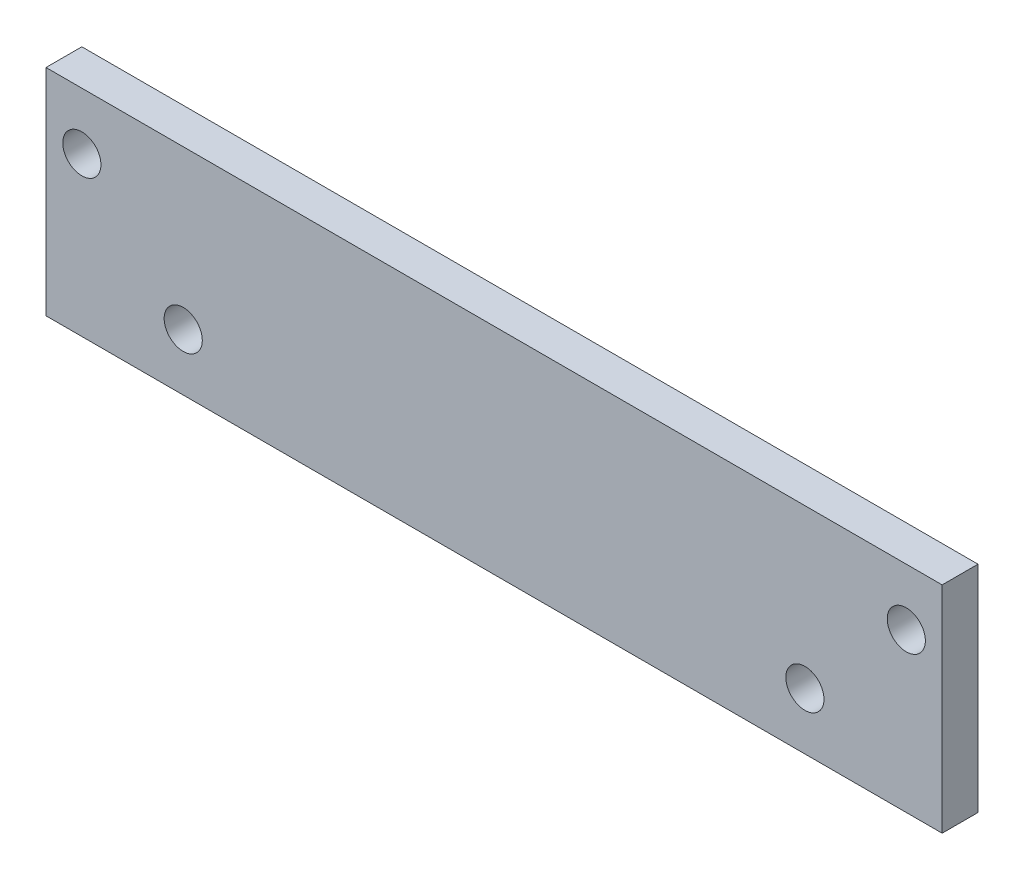
SolidWorks part; units mm, degrees
ref_plane "Front" through (0, 0, 0) normal (0, 0, 1) x (1, 0, 0)
ref_plane "Top" through (0, 0, 0) normal (0, 1, 0) x (1, 0, 0)
ref_plane "Right" through (0, 0, 0) normal (1, 0, 0) x (0, 0, -1)
sketch "Sketch1" plane through (0, 0, 0) normal (0, 0, 1) x (1, 0, 0)
  line L1 (-79.375, -19.05) -> (79.375, -19.05)
  line L2 (-79.375, -19.05) -> (-79.375, 19.05)
  line L3 (-79.375, 19.05) -> (79.375, 19.05)
  line L4 (79.375, -19.05) -> (79.375, 19.05)
  line L5 (-79.375, -19.05) -> (79.375, 19.05) construction
  line L6 (-79.375, 19.05) -> (79.375, -19.05) construction
  point P0 (0, 0)
  dimension "D1" = 158.75
  dimension "D2" = 38.1
extrude "Boss-Extrude1" add sketch "Sketch1" along normal blind 6.35
sketch "Sketch2" plane through (0, 0, 6.35) normal (0, 0, 1) x (1, 0, 0)
  line L0 (-73.025, 19.05) -> (-73.025, 8.9803) construction
  line L1 (79.375, 19.05) -> (-79.375, 19.05) construction
  line L2 (-73.025, 8.9803) -> (-55.0645, -8.9803) construction
  line L3 (-55.0645, -8.9803) -> (-55.0645, -19.05) construction
  line L4 (-79.375, -19.05) -> (79.375, -19.05) construction
  line L5 (-79.375, 19.05) -> (-79.375, -19.05) construction
  dimension "D1" = 135
  dimension "D2" = 25.4
  dimension "D3" = 6.35
hole_wizard "1/4 Clearance Hole1" positions "Sketch4" profile "Sketch3" hole size "1/4" standard "ANSI Inch" end condition through all
sketch "Sketch4" plane through (0, 0, 6.35) normal (0, 0, 1) x (1, 0, 0)
  point P0 (-73.025, 8.9803)
  point P3 (-55.0645, -8.9803)
sketch "Sketch3" plane through (-73.025, 8.9803, 6.35) normal (1, 0, 0) x (0, -1, 0)
  line L0 (0, 0) -> (0, 6.35)
  line L1 (0, 6.35) -> (3.3782, 6.35)
  line L2 (3.3782, 6.35) -> (3.3782, 0)
  line L5 (3.3782, 0) -> (0, 0)
  line L11 (0, -6.35) -> (0, 107.95) construction
  dimension "Thru Hole Dia." = 6.7564
  dimension "Thru Hole Depth" = 6.35
mirror "Mirror1" about plane through (0, 0, 0) normal (1, 0, 0) of "1/4 Clearance Hole1"
